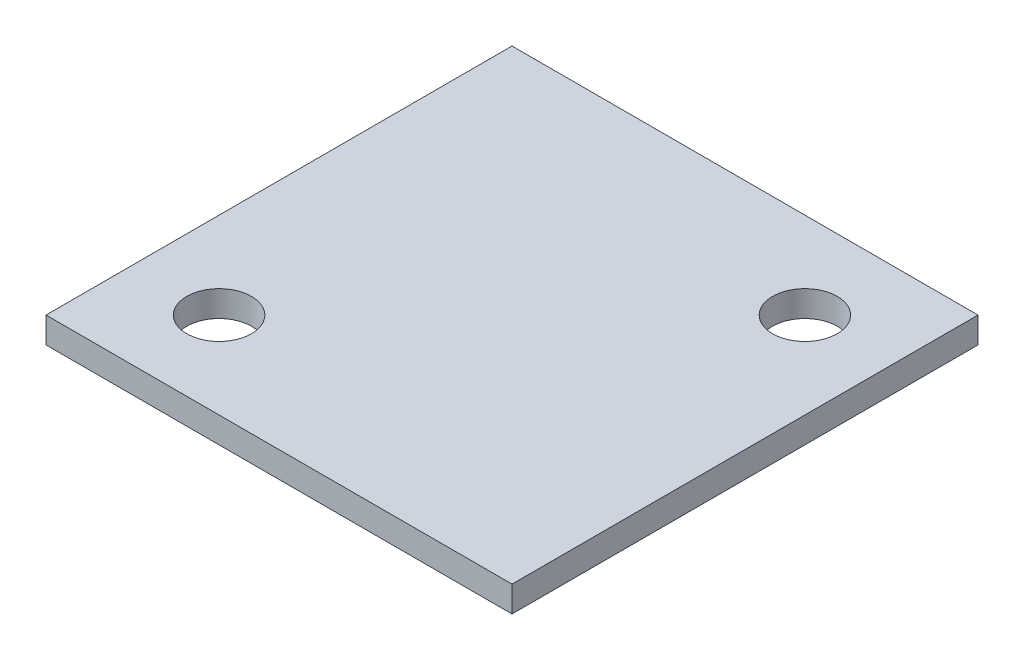
SolidWorks part; units mm, degrees
ref_plane "Front Plane" through (0, 0, 0) normal (0, 0, 1) x (1, 0, 0)
ref_plane "Top Plane" through (0, 0, 0) normal (0, 1, 0) x (1, 0, 0)
ref_plane "Right Plane" through (0, 0, 0) normal (1, 0, 0) x (0, 0, -1)
sketch "Sketch1" plane through (0, 0, 0) normal (0, 1, 0) x (1, 0, 0)
  line L1 (-90, -90) -> (90, -90)
  line L2 (-90, -90) -> (-90, 90)
  line L3 (-90, 90) -> (90, 90)
  line L4 (90, -90) -> (90, 90)
  line L5 (-90, -90) -> (90, 90) construction
  line L6 (-90, 90) -> (90, -90) construction
  point P0 (0, 0)
  dimension "D1" = 180
extrude "Boss-Extrude1" add sketch "Sketch1" along normal blind 10
sketch "Sketch2" plane through (0, 0, 0) normal (0, -1, 0) x (-1, 0, 0)
  line L3 (-56.5685, 56.5685) -> (-90, 90) construction
  line L5 (56.5685, -56.5685) -> (90, -90) construction
  circle A1 centre (-56.5685, 56.5685) radius 12.5
  circle A2 centre (56.5685, -56.5685) radius 12.5
  point P6 (0, 0)
  dimension "D1" = 160
  dimension "D2" = 25
extrude "Cut-Extrude1" cut sketch "Sketch2" against normal up to surface (10 mm away) up to face at (0, 10, 0)
